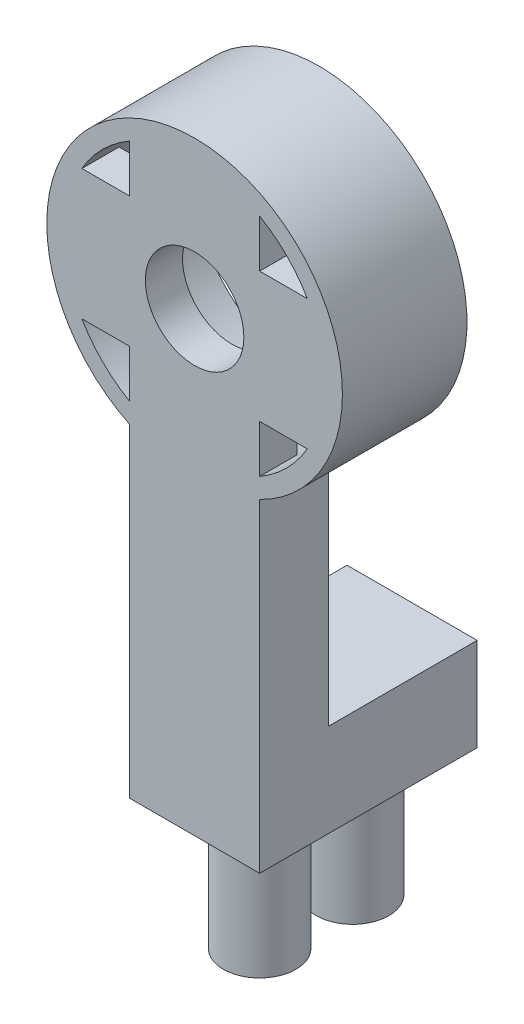
SolidWorks part; units mm, degrees
ref_plane "Front Plane" through (0, 0, 0) normal (0, 0, 1) x (1, 0, 0)
ref_plane "Top Plane" through (0, 0, 0) normal (0, 1, 0) x (1, 0, 0)
ref_plane "Right Plane" through (0, 0, 0) normal (1, 0, 0) x (0, 0, -1)
sketch "Sketch1" plane through (0, 0, 0) normal (0, 0, 1) x (1, 0, 0)
  line L5 (0, -17.5) -> (12.7696, -17.5) construction
  line L26 (0, 0) -> (0, -35) construction
  line L32 (0, 3.5) -> (7.1381, 3.5)
  line L33 (7.1381, 3.5) -> (-7.1381, 3.5)
  line L34 (0, -3.5) -> (7.1381, -3.5)
  line L35 (7.1381, -3.5) -> (-7.1381, -3.5)
  line L36 (3.5, -35) -> (3.5, -41.0622)
  line L37 (-3.5, -35) -> (-3.5, -41.0622)
  line L38 (-3.5, 0) -> (-3.5, 6.0622)
  line L45 (-3.5, 0) -> (-3.5, -35)
  line L47 (3.5, 0) -> (3.5, -35)
  line L48 (3.5, 0) -> (3.5, 6.0622)
  line L49 (7.1381, -31.5) -> (-7.1381, -31.5)
  line L50 (0, -31.5) -> (7.1381, -31.5)
  line L51 (7.1381, -38.5) -> (-7.1381, -38.5)
  line L52 (0, -38.5) -> (7.1381, -38.5)
  circle A0 centre (0, 0) radius 7.95
  circle A1 centre (0, 0) radius 3.5
  circle A2 centre (0, 0) radius 7
  circle A6 centre (0, 0) radius 1.5
  circle A11 centre (0, -35) radius 1.5
  circle A12 centre (0, -35) radius 7
  circle A13 centre (0, -35) radius 3.5
  circle A14 centre (0, -35) radius 7.95
  point P20 (0, -35)
  point P34 (0, -35)
  point P42 (0, 0)
  dimension "D1" = 15.9
  dimension "D2" = 7
  dimension "D6" = 14
  dimension "D9" = 3
  dimension "D3" = 7
  dimension "D7" = 35
extrude "Boss-Extrude4" add sketch "Sketch1" along normal blind 3 contours L48 A2 L38 L33 L32 | A2 L32 A0 L33 | L45 A14 L47 A0 | A14 L51 A12 | A12 L36 L51 L37 | A14 L49 A12 L51 | L36 A13 L51 | L51 A13 L37 | A14 L51 A12 L49 | A13 A11 | L45 A13 L49 | L49 A13 L47 | A12 L45 L49 L47 | A14 L49 A12 L45 | A14 L47 A12 L49 | A14 L45 A12 L47 | A12 L51 L37 L45 L49 | A12 L50 L47 L36 L52 | L45 A2 L47 L34 L35 | A2 L45 A0 L47 | A2 L47 A0 L34 | A2 L34 A0 L32 | A2 L33 A0 L35 | A2 L35 A0 L45 | L33 A2 L35 L45 L38 | L35 A2 L33 L48 L47 | A1 L34 L47 | A1 A6 | A1 L45 L35 | A1 L33 L38 | A1 L48 L32 region at (0, 5.1101, 0) region at (-2.7182, 2.7182, 0) region at (2.7182, 2.7182, 0) region at (2.4049, 2.4049, 0) region at (5.1101, 0, 0) region at (-5.1101, 0, 0) region at (2.7182, -2.7182, 0) region at (-2.7182, -2.7182, 0) region at (5.0555, 5.0555, 0) region at (7.1812, 0, 0) region at (-7.1812, 0, 0) region at (0, -5.1101, 0) region at (-5.2259, -5.2259, 0) region at (5.2259, -5.2259, 0) region at (0, -7.1812, 0) region at (0, -17.5, 0) region at (5.2259, -29.7741, 0) region at (0, -27.8188, 0) region at (-5.2259, -29.7741, 0) region at (0, -29.8899, 0) region at (7.1812, -35, 0) region at (-7.1812, -35, 0) region at (5.1101, -35, 0) region at (2.7182, -32.2818, 0) region at (-2.7182, -32.2818, 0) region at (-5.1101, -35, 0) region at (-6.6001, -38.6495, 0) region at (2.4049, -37.4049, 0) region at (2.7182, -37.7182, 0) region at (-2.7182, -37.7182, 0) region at (0, -40.1101, 0)
sketch "Sketch3" plane through (0, 0, 0) normal (0, 0, -1) x (-1, 0, 0)
  line L0 (-3.5, 6.0622) -> (-3.5, 3.5)
  line L1 (-3.5, 3.5) -> (-6.0622, 3.5)
  line L2 (-3.5, -6.0622) -> (-3.5, -3.5)
  line L3 (-3.5, -3.5) -> (-6.0622, -3.5)
  line L4 (3.5, -6.0622) -> (3.5, -3.5)
  line L5 (3.5, -3.5) -> (6.0622, -3.5)
  line L6 (3.5, 6.0622) -> (3.5, 3.5)
  line L7 (3.5, 3.5) -> (6.0622, 3.5)
  line L8 (0, 0) -> (0, -35) construction
  line L9 (0, -35) -> (0, -17.5) construction
  line L10 (0, -17.5) -> (14.5774, -17.5) construction
  line L11 (-3.5, 3.5) -> (-6.0622, 3.5)
  line L12 (-3.5, 6.0622) -> (-3.5, 3.5)
  line L13 (-3.5, -3.5) -> (-6.0622, -3.5)
  line L14 (-3.5, -6.0622) -> (-3.5, -3.5)
  line L15 (3.5, -3.5) -> (6.0622, -3.5)
  line L16 (3.5, -6.0622) -> (3.5, -3.5)
  line L17 (3.5, 3.5) -> (6.0622, 3.5)
  line L18 (3.5, 6.0622) -> (3.5, 3.5)
  line L19 (3.5, -41.0622) -> (3.5, -38.5)
  line L20 (3.5, -38.5) -> (6.0622, -38.5)
  line L21 (3.5, -28.9378) -> (3.5, -31.5)
  line L22 (3.5, -31.5) -> (6.0622, -31.5)
  line L23 (-3.5, -28.9378) -> (-3.5, -31.5)
  line L24 (-3.5, -31.5) -> (-6.0622, -31.5)
  line L25 (-3.5, -41.0622) -> (-3.5, -38.5)
  line L26 (-3.5, -38.5) -> (-6.0622, -38.5)
  line L27 (3.5, -38.5) -> (6.0622, -38.5)
  line L28 (3.5, -41.0622) -> (3.5, -38.5)
  line L29 (3.5, -31.5) -> (6.0622, -31.5)
  line L30 (3.5, -28.9378) -> (3.5, -31.5)
  line L31 (-3.5, -31.5) -> (-6.0622, -31.5)
  line L32 (-3.5, -28.9378) -> (-3.5, -31.5)
  line L33 (-3.5, -38.5) -> (-6.0622, -38.5)
  line L34 (-3.5, -41.0622) -> (-3.5, -38.5)
  circle A0 centre (0, 0) radius 1.5
  circle A1 centre (0, 0) radius 7.95
  circle A2 centre (0, 0) radius 7
  circle A3 centre (0, -35) radius 7
  circle A4 centre (0, -35) radius 7.95
  circle A5 centre (0, -35) radius 1.5
  line M2 (3.5, -38.5) -> (6.0622, -38.5)
  arc M3 (6.0622, -38.5) -> (3.5, -41.0622) centre (0, -35) cw
  line M4 (3.5, -41.0622) -> (3.5, -38.5)
  line M5 (-3.5, -38.5) -> (-3.5, -41.0622)
  arc M6 (-3.5, -41.0622) -> (-6.0622, -38.5) centre (0, -35) cw
  line M7 (-6.0622, -38.5) -> (-3.5, -38.5)
  arc M9 (3.5, -7.1381) -> (-3.5, -7.1381) centre (0, 0) ccw
  arc M11 (-3.5, -27.8619) -> (3.5, -27.8619) centre (0, -35) ccw
  line M12 (6.0622, -31.5) -> (3.5, -31.5)
  line M13 (3.5, -31.5) -> (3.5, -28.9378)
  arc M14 (3.5, -28.9378) -> (6.0622, -31.5) centre (0, -35) cw
  arc M15 (-3.5, -6.0622) -> (-6.0622, -3.5) centre (0, 0) cw
  line M16 (-6.0622, -3.5) -> (-3.5, -3.5)
  line M17 (-3.5, -3.5) -> (-3.5, -6.0622)
  line M18 (-3.5, -31.5) -> (-6.0622, -31.5)
  arc M19 (-6.0622, -31.5) -> (-3.5, -28.9378) centre (0, -35) cw
  line M20 (-3.5, -28.9378) -> (-3.5, -31.5)
  line M21 (3.5, -3.5) -> (6.0622, -3.5)
  arc M22 (6.0622, -3.5) -> (3.5, -6.0622) centre (0, 0) cw
  line M23 (3.5, -6.0622) -> (3.5, -3.5)
  line M24 (6.0622, 3.5) -> (3.5, 3.5)
  line M25 (3.5, 3.5) -> (3.5, 6.0622)
  arc M26 (3.5, 6.0622) -> (6.0622, 3.5) centre (0, 0) cw
  arc M27 (-6.0622, 3.5) -> (-3.5, 6.0622) centre (0, 0) cw
  line M28 (-3.5, 6.0622) -> (-3.5, 3.5)
  line M29 (-3.5, 3.5) -> (-6.0622, 3.5)
  circle M30 centre (0, 0) radius 1.5
  circle M31 centre (0, -35) radius 1.5
  dimension "D1" = 15.9
extrude "Boss-Extrude5" add sketch "Sketch3" along normal blind 3 contours A1 A2 M9 M26 M22 M15 M27 | A2 M25 M28 M29 M16 M17 M23 M21 M24 M30 | A3 M4 M2 M12 M13 M20 M18 M7 M5 M31 | A4 A3 M11 M3 M6 M19 M14 region at (0, 6.802, 0) region at (0, -41.802, 0) region at (-6.5556, -4.0868, 0) region at (4.0868, -41.5556, 0)
sketch "Sketch4" plane through (0, 0, 3) normal (0, 0, 1) x (1, 0, 0)
  line L0 (0, 0) -> (0, -35) construction
  line L1 (0, -35) -> (0, 0) construction
  line L2 (0, -17.5) -> (19.6941, -17.5) construction
  circle A1 centre (0, -35) radius 2.5
  circle A2 centre (0, 0) radius 2.5
  dimension "D2" = 5
extrude "Cut-Extrude1" cut sketch "Sketch4" against normal blind 1.5
sketch "Sketch5" plane through (0, 0, -3) normal (0, 0, -1) x (-1, 0, 0)
  circle A0 centre (0, 0) radius 7
extrude "Cut-Extrude2" cut sketch "Sketch5" against normal blind 4
sketch "Sketch6" plane through (0, 0, -3) normal (0, 0, -1) x (-1, 0, 0)
  circle A0 centre (0, -35) radius 7.95
extrude "Cut-Extrude3" cut sketch "Sketch6" against normal blind 1
sketch "Sketch7" plane through (0, 0, 1.5) normal (0, 0, 1) x (1, 0, 0)
  circle A0 centre (0, -35) radius 2.5
extrude "Cut-Extrude4" cut sketch "Sketch7" against normal blind 0.5
sketch "Sketch8" plane through (0, 0, -3) normal (0, 0, -1) x (-1, 0, 0)
  circle A0 centre (0, 0) radius 7.95
  circle A1 centre (0, 0) radius 7
extrude "Boss-Extrude6" add sketch "Sketch8" along normal blind 0.7
sketch "Sketch9" plane through (0, 0, -2) normal (0, 0, -1) x (-1, 0, 0)
  line L0 (-3.5, -28.9378) -> (-3.5, -31.5)
  line L1 (-3.5, -31.5) -> (-6.0622, -31.5)
  line L2 (-6.0622, -38.5) -> (-3.5, -38.5)
  line L3 (-3.5, -38.5) -> (-3.5, -41.0622)
  line L4 (6.0622, -38.5) -> (3.5, -38.5)
  line L5 (3.5, -38.5) -> (3.5, -41.0622)
  line L6 (3.5, -28.9378) -> (3.5, -31.5)
  line L7 (3.5, -31.5) -> (6.0622, -31.5)
  circle A0 centre (0, -35) radius 7.95
  circle A1 centre (0, -35) radius 7
  circle A2 centre (0, -35) radius 1.5
  line M1 (6.0622, -31.5) -> (3.5, -31.5)
  line M2 (3.5, -31.5) -> (3.5, -28.9378)
  arc M3 (3.5, -28.9378) -> (6.0622, -31.5) centre (0, -35) cw
  arc M4 (-3.5, -41.0622) -> (-6.0622, -38.5) centre (0, -35) cw
  line M5 (-6.0622, -38.5) -> (-3.5, -38.5)
  line M6 (-3.5, -38.5) -> (-3.5, -41.0622)
  arc M7 (6.0622, -38.5) -> (3.5, -41.0622) centre (0, -35) cw
  line M8 (3.5, -41.0622) -> (3.5, -38.5)
  line M9 (3.5, -38.5) -> (6.0622, -38.5)
  circle M10 centre (0, -35) radius 7.95
  line M11 (-3.5, -31.5) -> (-6.0622, -31.5)
  arc M12 (-6.0622, -31.5) -> (-3.5, -28.9378) centre (0, -35) cw
  line M13 (-3.5, -28.9378) -> (-3.5, -31.5)
  circle M14 centre (0, -35) radius 1.5
extrude "Boss-Extrude8" add sketch "Sketch9" along normal blind 0.7 contours A1 M2 M13 M11 M5 M6 M8 M9 M1 M14 | A1 M10 M3 M7 M4 M12 region at (0, -28.198, -2) region at (7.7251, -35, -2)
sketch "Sketch10" plane through (0, 0, 0) normal (0, 0, -1) x (-1, 0, 0)
  line L2 (-3.5, -7.1381) -> (-3.5, -27.8619)
  line L4 (3.5, -7.1381) -> (3.5, -27.8619)
  circle A0 centre (0, 0) radius 7.95
  circle A1 centre (0, -35) radius 7.95
  line M1 (-3.5, -7.1381) -> (-3.5, -27.8619)
  arc M2 (-3.5, -27.8619) -> (3.5, -27.8619) centre (0, -35) cw
  line M3 (3.5, -27.8619) -> (3.5, -7.1381)
  arc M4 (3.5, -7.1381) -> (-3.5, -7.1381) centre (0, 0) cw
extrude "Boss-Extrude9" add sketch "Sketch10" along normal blind 0.7 contours M4 M1 M2 M3 region at (0, -17.5, 0)
sketch "Sketch15" plane through (0, 0, -2.7) normal (0, 0, -1) x (-1, 0, 0)
  circle A0 centre (0, -35) radius 7
  circle A1 centre (0, -35) radius 4.9497
extrude "Boss-Extrude12" add sketch "Sketch15" against normal blind 5.7
sketch "Sketch16" plane through (0, 0, -2.7) normal (0, 0, -1) x (-1, 0, 0)
  line L1 (-3.5, -31.5) -> (3.5, -31.5)
  line L2 (-3.5, -31.5) -> (-3.5, -38.5)
  line L3 (-3.5, -38.5) -> (3.5, -38.5)
  line L4 (3.5, -31.5) -> (3.5, -38.5)
  line L5 (-3.5, -31.5) -> (3.5, -38.5) construction
  line L6 (-3.5, -38.5) -> (3.5, -31.5) construction
  point P0 (0, -35)
  dimension "D1" = 7
  dimension "D2" = 7
extrude "Cut-Extrude7" cut sketch "Sketch16" against normal blind 5.7
sketch "Sketch17" plane through (0, 0, -2.7) normal (0, 0, -1) x (-1, 0, 0)
  line L0 (0, 0) -> (0, -24.55) construction
  line L2 (-11.0265, -24.55) -> (10.0772, -24.55)
  line L3 (-11.0265, -24.55) -> (-11.0265, -44.0073)
  line L4 (-11.0265, -44.0073) -> (10.0772, -44.0073)
  line L5 (10.0772, -24.55) -> (10.0772, -44.0073)
  dimension "D1" = 24.55
extrude "Cut-Extrude8" cut sketch "Sketch17" against normal blind 10
sketch "Sketch18" plane through (0, -24.55, 0) normal (0, -1, 0) x (1, 0, 0)
  line L0 (0, 3) -> (0, 2.8) construction
  line L1 (3.5, 3) -> (-3.5, 3) construction
  line L2 (0, 2.8) -> (0, -8.7) construction
  line L4 (3.5, -0.7) -> (-3.5, -0.7)
  line L5 (3.5, -0.7) -> (3.5, -8.7)
  line L6 (3.5, -8.7) -> (-3.5, -8.7)
  line L7 (-3.5, -0.7) -> (-3.5, -8.7)
  dimension "D1" = 0.2
  dimension "D2" = 11.5
  dimension "D3" = 8
extrude "Boss-Extrude13" add sketch "Sketch18" against normal blind 5
sketch "Sketch19" plane through (0, -24.55, 0) normal (0, -1, 0) x (1, 0, 0)
  line L1 (-3.5, -8.7) -> (3.5, -8.7) construction
  line L3 (3.5, -8.7) -> (3.5, 3) construction
  line L9 (3.5, 3) -> (-3.5, 3) construction
  line L10 (-3.45, 3) -> (3.45, 3) construction
  line L11 (-3.45, 3) -> (-3.45, -8.5) construction
  line L12 (-3.45, -8.5) -> (3.45, -8.5) construction
  line L13 (3.45, 3) -> (3.45, -8.5) construction
  line L14 (-3.5, 3) -> (-3.5, -0.7) construction
  line L16 (-2, 1.5) -> (2, 1.5) construction
  line L17 (-2, 1.5) -> (-2, -7.5) construction
  line L18 (-2, -7.5) -> (2, -7.5) construction
  line L19 (2, 1.5) -> (2, -7.5) construction
  circle A0 centre (0, -5.5) radius 1.95
  circle A1 centre (0, -0.5) radius 1.95
  dimension "D2" = 3.9
  dimension "D3" = 3.2
  dimension "D4" = 3.5
  dimension "D1" = 0.05
  dimension "D5" = 2
  dimension "D6" = 0.05
  dimension "D7" = 11.5
  dimension "D8" = 1.5
  dimension "D9" = 1
  dimension "D10" = 4
  dimension "D11" = 1.45
extrude "Boss-Extrude14" add sketch "Sketch19" along normal blind 7
sketch "Sketch20" plane through (0, 0, 3) normal (0, 0, 1) x (1, 0, 0)
  circle A0 centre (0, 0) radius 2.65
  dimension "D1" = 5.3
extrude "Cut-Extrude9" cut sketch "Sketch20" against normal blind 10
